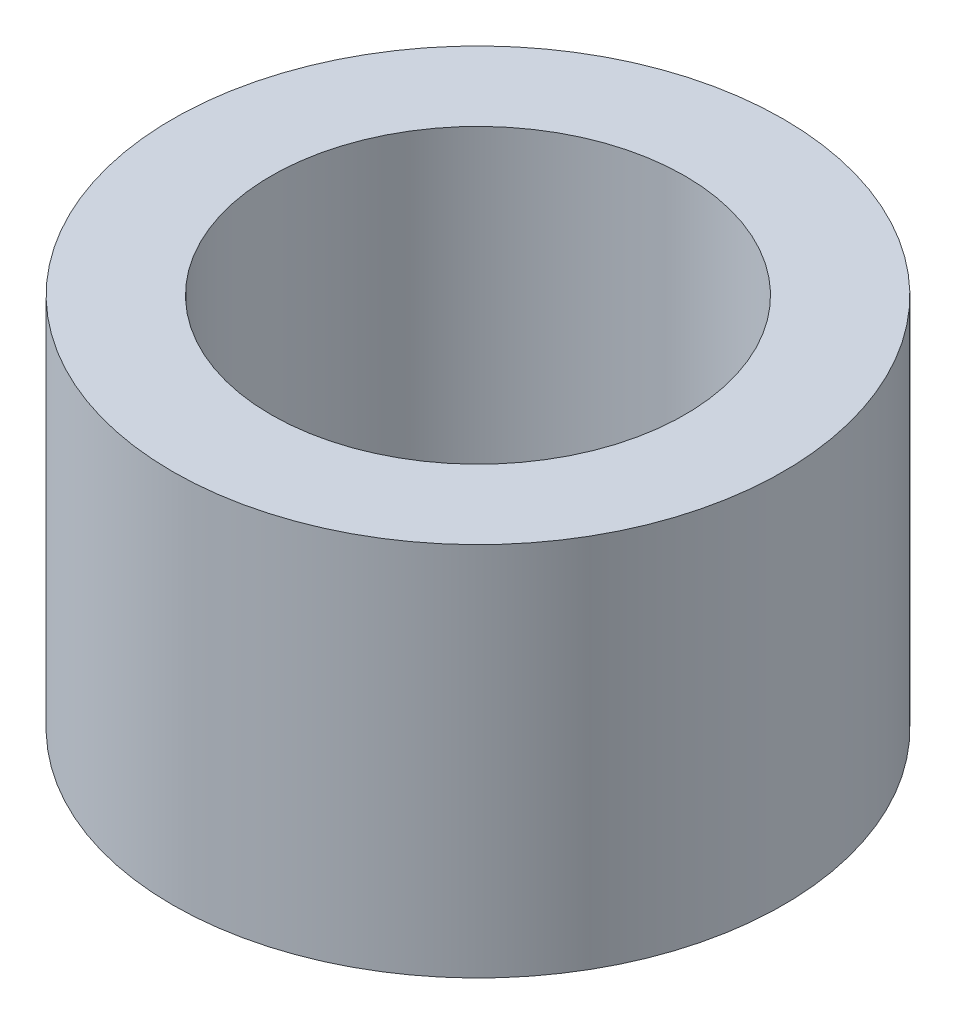
SolidWorks part; units mm, degrees
ref_plane "Front Plane" through (0, 0, 0) normal (0, 0, 1) x (1, 0, 0)
ref_plane "Top Plane" through (0, 0, 0) normal (0, 1, 0) x (1, 0, 0)
ref_plane "Right Plane" through (0, 0, 0) normal (1, 0, 0) x (0, 0, -1)
sketch "Sketch1" plane through (0, 0, 0) normal (0, 1, 0) x (1, 0, 0)
  circle A0 centre (0, 0) radius 4.2
  circle A1 centre (0, 0) radius 6.2
  dimension "D1" = 8.4
  dimension "D2" = 2
extrude "Boss-Extrude1" add sketch "Sketch1" along normal blind 7.62
